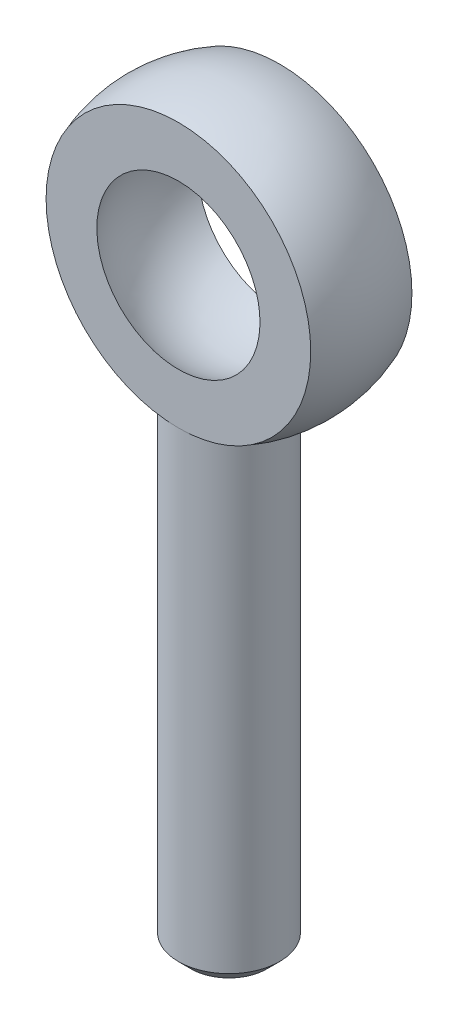
SolidWorks part; units mm, degrees
material "Plain Carbon Steel"
ref_plane "Front Plane" through (0, 0, 0) normal (0, 0, 1) x (1, 0, 0)
ref_plane "Top Plane" through (0, 0, 0) normal (0, 1, 0) x (1, 0, 0)
ref_plane "Right Plane" through (0, 0, 0) normal (1, 0, 0) x (0, 0, -1)
sketch "Sketch2" plane through (0, 0, 0) normal (1, 0, 0) x (0, 0, -1)
  line L0 (0, 15.4744) -> (0, -15.7624) construction
  line L1 (0, 7.5311) -> (0, -7.5311)
  arc A0 (0, 7.5311) -> (0, -7.5311) centre (0, 0) cw
  point P6 (0, -14.2606)
  dimension "D1" = 7.5311
sketch "Sketch3" plane through (0, 0, 0) normal (1, 0, 0) x (0, 0, -1)
  line L0 (-8.1466, 0) -> (8.1466, 0) construction
  line L1 (0, 31.115) -> (0, -31.115) construction
  line L2 (-3.9687, 10.3796) -> (-3.9687, 0)
  line L3 (-3.9687, 0) -> (3.9688, 0)
  line L4 (3.9688, 0) -> (3.9688, 10.3796)
  arc A0 (-3.9687, 10.3796) -> (3.9688, 10.3796) centre (0, 0) cw
  point P8 (0, 11.1125)
  dimension "D2" = 7.9375
  dimension "D1" = 11.1125
revolve "Revolve2" add sketch "Sketch3"
revolve "Cut-Revolve2" cut sketch "Sketch2" angle 360 about L0
sketch "Sketch4" plane through (0, 0, 0) normal (1, 0, 0) x (0, 0, -1)
  line L0 (0, -11.1125) -> (0, -35.6534) construction
  arc A0 (-3.9687, -10.3796) -> (3.9688, -10.3796) centre (0, 0) ccw construction
ref_plane "Plane1" through (0, -11.1125, 0) normal (0, 1, 0) x (-1, 0, 0)
sketch "Sketch5" plane through (0, -11.1125, 0) normal (0, 1, 0) x (-1, 0, 0)
  circle A0 centre (0, 0) radius 3.9688
  dimension "D1" = 7.9375
extrude "Extrude2" add sketch "Sketch5" against normal blind 36.52 and the other way blind 3
cosmetic thread "Cosmetic Thread1" parameters "D1"=31.75, "D2"=7.1438
chamfer "Chamfer1" distance 1 angle 45 1 edges at (0, -47.6325, 3.9688)
sketch "Sketch6" plane through (0, 0, 0) normal (1, 0, 0) x (0, 0, -1)
  line L0 (0, 18.0632) -> (0, -54.6469) construction
  line L1 (10.0987, 0) -> (-10.0987, 0) construction
  line L2 (0, -11.1125) -> (0, -35.6534) construction
  line L3 (-2.9687, -47.6325) -> (2.9687, -47.6325) construction
  point P5 (0, 0)
  point P6 (0, -31.6325)
  dimension "D1" = 16
ref_plane "PlaneLengthTop" through (0, 11.1125, 0) normal (0, 1, 0) x (1, 0, 0)
